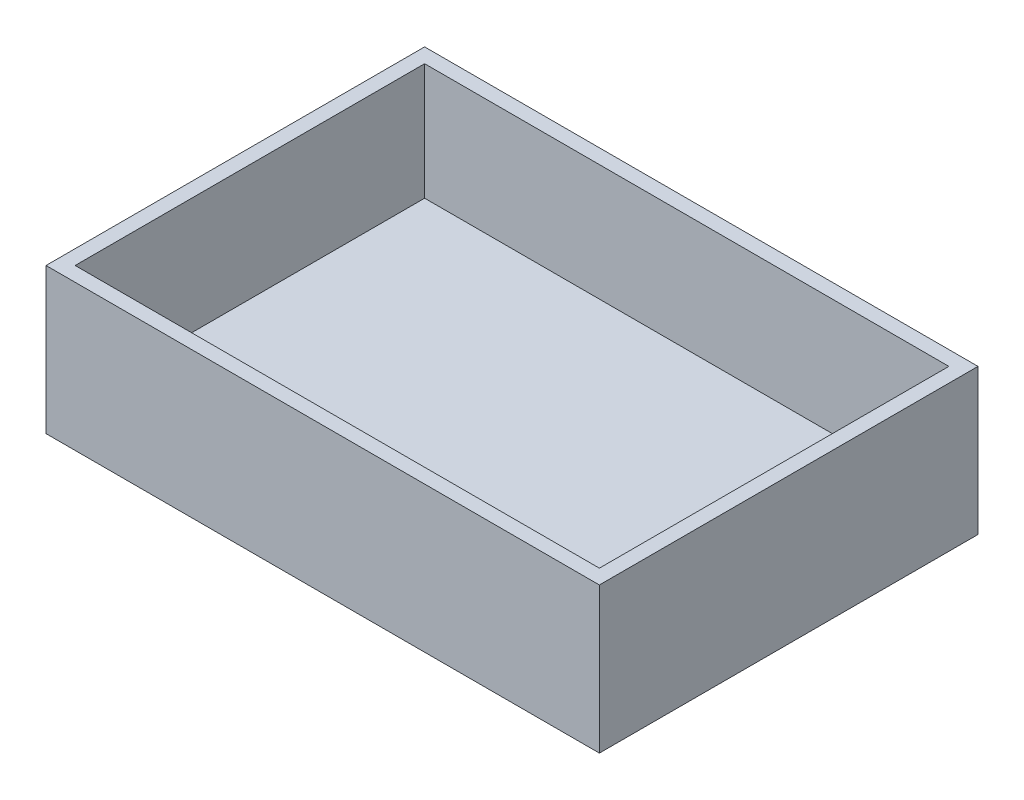
SolidWorks part; units mm, degrees
ref_plane "Front Plane" through (0, 0, 0) normal (0, 0, 1) x (1, 0, 0)
ref_plane "Top Plane" through (0, 0, 0) normal (0, 1, 0) x (1, 0, 0)
ref_plane "Right Plane" through (0, 0, 0) normal (1, 0, 0) x (0, 0, -1)
sketch "Sketch1" plane through (0, 0, 0) normal (0, 1, 0) x (1, 0, 0)
  line L0 (10, -10) -> (10, 110)
  line L1 (0, 0) -> (-160, 0)
  line L2 (0, 0) -> (0, 100)
  line L3 (0, 100) -> (-160, 100)
  line L4 (-160, 0) -> (-160, 100)
  line L9 (10, 110) -> (-170, 110)
  line L10 (-170, -10) -> (-170, 110)
  line L11 (10, -10) -> (-170, -10)
  line L12 (15, -15) -> (15, 115)
  line L13 (15, 115) -> (-175, 115)
  line L14 (-175, -15) -> (-175, 115)
  line L15 (15, -15) -> (-175, -15)
  point P9 (0, 0)
  dimension "D1" = 100
  dimension "D2" = 160
  dimension "D3" = 10
  dimension "D4" = 5
extrude "Boss-Extrude1" add sketch "Sketch1" along normal blind 10 contours L14 L13 L12 L15
extrude "Boss-Extrude2" add sketch "Sketch1<7>" along normal blind 50 contours L15 L12 L13 L14 L0 L11 L10 L9 region at (-80, 0, 12.6978)
sketch "Sketch1<7>" plane through (0, 0, 0) normal (0, 1, 0) x (1, 0, 0) same geometry as "Sketch1"
